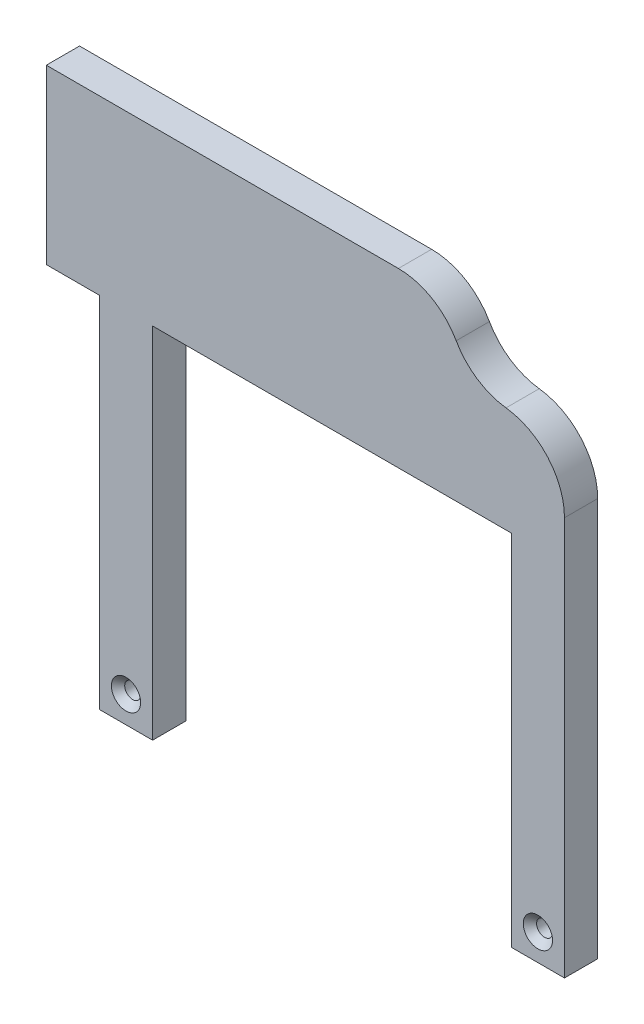
SolidWorks part; units mm, degrees
ref_plane "Plan de face" through (0, 0, 0) normal (0, 0, 1) x (1, 0, 0)
ref_plane "Plan de dessus" through (0, 0, 0) normal (0, 1, 0) x (1, 0, 0)
ref_plane "Plan de droite" through (0, 0, 0) normal (1, 0, 0) x (0, 0, -1)
sketch "Esquisse1" plane through (0, 0, 0) normal (0, 0, 1) x (1, 0, 0)
  line L36 (0, 0) -> (0, 54)
  line L41 (0, 140) -> (120, 140)
  line L42 (120, 140) -> (120, 130)
  line L43 (120, 130) -> (30, 130)
  line L44 (30, 130) -> (30, 80)
  line L45 (30, 80) -> (70, 80)
  line L46 (70, 80) -> (70, 0)
  line L47 (70, 0) -> (62, 0)
  line L48 (62, 0) -> (62, 54)
  line L49 (62, 54) -> (8, 54)
  line L50 (0, 0) -> (8, 0)
  line L51 (8, 0) -> (8, 54)
  line L52 (0, 80) -> (-8, 80)
  line L53 (-8, 80) -> (-8, 54)
  line L54 (-8, 54) -> (0, 54)
  line L55 (0, 80) -> (0, 140)
  dimension "D2" = 8
  dimension "D3" = 54
  dimension "D4" = 8
  dimension "D5" = 10
  dimension "D6" = 140
  dimension "D7" = 8
  dimension "D8" = 120
  dimension "D10" = 90
  dimension "D11" = 50
  dimension "D12" = 54
extrude "Boss.-Extru.1" add sketch "Esquisse1" along normal blind 5
sketch "Esquisse2" plane through (0, 0, 5) normal (0, 0, 1) x (1, 0, 0)
  line L0 (0, 0) -> (8, 0) construction
  line L1 (8, 0) -> (8, 54) construction
  line L2 (62, 0) -> (70, 0) construction
  line L3 (70, 0) -> (70, 80) construction
  circle A0 centre (4, 4) radius 1
  circle A1 centre (66, 4) radius 1
  dimension "D1" = 4
  dimension "D3" = 2
  dimension "D6" = 2
  dimension "D2" = 4
  dimension "D4" = 4
  dimension "D5" = 4
hole_wizard "Fraisage pour vis à tête fraisée M21" positions "Esquisse3" profile "Esquisse4" countersink size "M2" standard "ISO" end condition through all
sketch "Esquisse3" plane through (0, 0, 5) normal (0, 0, 1) x (1, 0, 0)
  point P0 (4, 4)
  point P3 (66, 4)
sketch "Esquisse4" plane through (4, 4, 5) normal (1, 0, 0) x (0, -1, 0)
  line L0 (0, 0) -> (0, 5)
  line L1 (0, 5) -> (1.2, 5)
  line L2 (1.2, 5) -> (1.2, 1)
  line L3 (1.2, 1) -> (2.2, 0)
  line L5 (2.2, 0) -> (0, 0)
  line L6 (-1.2, 1) -> (-2.2, 0) construction
  line L11 (0, -6.35) -> (0, 107.95) construction
  dimension "Diamètre du perçage jusqu'au prochain" = 2.4
  dimension "Profondeur du perçage jusqu'au prochain" = 5
  dimension "Diamètre du fraisage entrant" = 4.4
  dimension "Angle du fraisage entrant" = 90
fillet "Congé1" [suppressed] radius 10
fillet "Congé2" radius 25 1 edges at (30, 130, 2.5)
sketch "Esquisse5" plane through (0, 0, 5) normal (0, 0, 1) x (1, 0, 0)
  line L1 (70, 80) -> (55, 80)
  line L2 (70, 80) -> (70, 70)
  line L3 (70, 70) -> (55, 70)
  line L4 (55, 80) -> (55, 70)
  dimension "D1" = 15
  dimension "D2" = 10
extrude "Enlèv. mat.-Extru.1" cut sketch "Esquisse5" against normal up to surface (5 mm away) up to face at (5.2, 4, 0)
sketch "Esquisse6" plane through (0, 0, 5) normal (0, 0, 1) x (1, 0, 0)
  line L0 (55, 130) -> (120, 130) construction
  line L1 (120, 140) -> (112, 140)
  line L2 (120, 140) -> (120, 130)
  line L3 (120, 130) -> (112, 130)
  line L4 (112, 140) -> (112, 130)
  dimension "D1" = 8
extrude "Enlèv. mat.-Extru.2" [suppressed] cut sketch "Esquisse6" against normal up to surface (5 mm away) up to face at (5.2, 4, 0)
fillet "Congé3" radius 10 2 edges at (70, 70, 2.5) (55, 80, 2.5)
fillet "Congé4" radius 10 1 edges at (55, 70, 2.5)
sketch "Esquisse7" plane through (0, 0, 5) normal (0, 0, 1) x (1, 0, 0)
  line L0 (0, 54) -> (0, 0) construction
  line L1 (120, 140) -> (0, 140)
  line L2 (120, 140) -> (120, 80)
  line L3 (120, 80) -> (0, 80)
  line L4 (0, 140) -> (0, 80)
  line L5 (45, 80) -> (30, 80) construction
extrude "Enlèv. mat.-Extru.3" cut sketch "Esquisse7" against normal up to surface (5 mm away) up to face at (5.2, 4, 0)
sketch "Esquisse8" [suppressed] plane through (0, 0, 5) normal (0, 0, 1) x (1, 0, 0)
  line L5 (0, 80) -> (-15, 80)
  line L6 (-15, 80) -> (-15, 54)
  line L7 (-15, 54) -> (0, 54)
  line L8 (0, 80) -> (0, 0) construction
  line L9 (8, 54) -> (62, 54) construction
  line L10 (0, 80) -> (0, 54)
  line L18 (45, 80) -> (0, 80)
  line L19 (0, 80) -> (0, 0)
  line L20 (0, 0) -> (8, 0)
  line L21 (8, 0) -> (8, 54)
  line L22 (8, 54) -> (62, 54)
  line L23 (62, 54) -> (62, 0)
  line L24 (62, 0) -> (70, 0)
  line L25 (70, 0) -> (70, 60)
  line L26 (45, 80) -> (0, 80)
  line L27 (0, 54) -> (0, 0)
  line L28 (0, 0) -> (8, 0)
  line L29 (8, 0) -> (8, 54)
  line L30 (8, 54) -> (62, 54)
  line L31 (62, 54) -> (62, 0)
  line L32 (62, 0) -> (70, 0)
  line L33 (70, 0) -> (70, 60)
  arc A3 (70, 60) -> (61.2017, 69.9275) centre (60, 60) ccw
  arc A4 (53.7017, 74.9275) -> (61.2017, 69.9275) centre (62.4034, 79.8551) ccw
  arc A5 (53.7017, 74.9275) -> (45, 80) centre (45, 70) ccw
  arc A6 (70, 60) -> (61.2017, 69.9275) centre (60, 60) ccw
  arc A7 (53.7017, 74.9275) -> (61.2017, 69.9275) centre (62.4034, 79.8551) ccw
  arc A8 (53.7017, 74.9275) -> (45, 80) centre (45, 70) ccw
  dimension "D1" = 15
  dimension "D2" = 0
